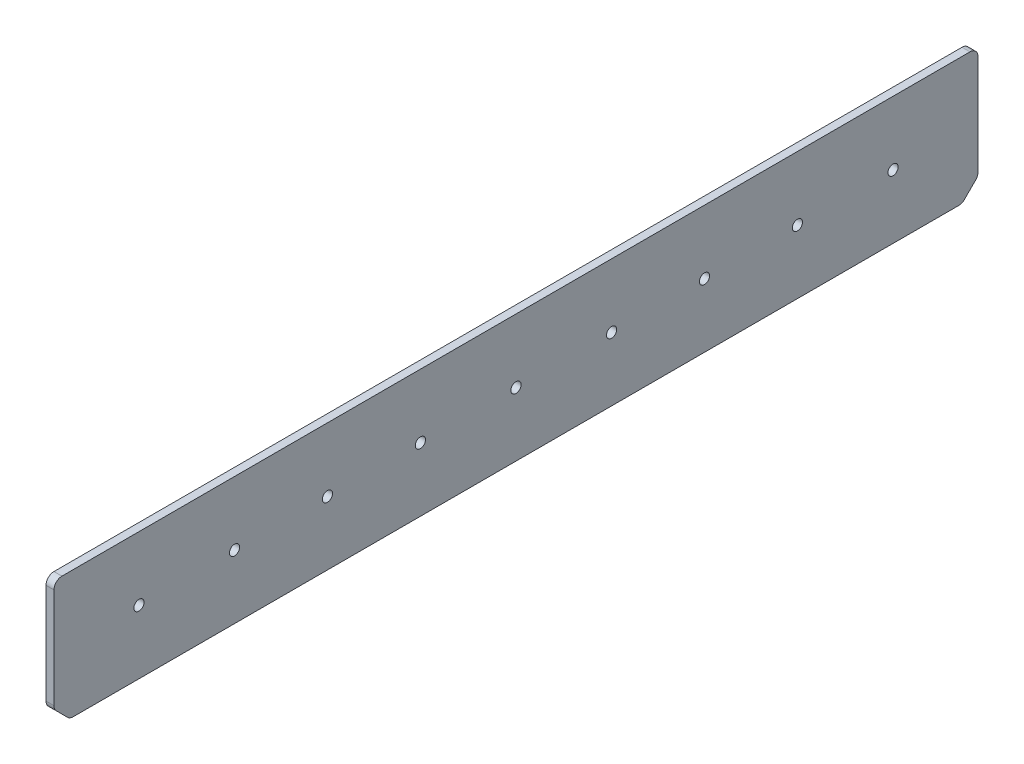
SolidWorks part; units mm, degrees
ref_plane "Front Plane" through (0, 0, 0) normal (0, 0, 1) x (1, 0, 0)
ref_plane "Top Plane" through (0, 0, 0) normal (0, 1, 0) x (1, 0, 0)
ref_plane "Right Plane" through (0, 0, 0) normal (1, 0, 0) x (0, 0, -1)
sketch "Sketch1" plane through (0, 0, 0) normal (1, 0, 0) x (0, 0, -1)
  line L1 (0, 0) -> (368.3, 0)
  line L2 (0, 0) -> (0, 50.8)
  line L3 (0, 50.8) -> (368.3, 50.8)
  line L4 (368.3, 0) -> (368.3, 50.8)
  dimension "D1" = 50.8
  dimension "D2" = 368.3
extrude "Boss-Extrude1" add sketch "Sketch1" along normal blind 3.175
sketch "Sketch2" plane through (3.175, 0, 0) normal (1, 0, 0) x (0, 0, -1)
  circle A0 centre (334.4333, 25.4) radius 2.032 construction
  circle A1 centre (296.3333, 25.4) radius 2.032 construction
  circle A2 centre (259.2917, 25.4) radius 2.032 construction
  circle A3 centre (222.25, 25.4) radius 2.032 construction
  circle A4 centre (184.15, 25.4) radius 2.032 construction
  circle A5 centre (146.05, 25.4) radius 2.032 construction
  circle A6 centre (109.0083, 25.4) radius 2.032 construction
  circle A7 centre (71.9667, 25.4) radius 2.032 construction
  circle A8 centre (33.8667, 25.4) radius 2.032 construction
  circle A9 centre (334.4333, 25.4) radius 2.032
  circle A10 centre (296.3333, 25.4) radius 2.032
  circle A11 centre (259.2917, 25.4) radius 2.032
  circle A12 centre (222.25, 25.4) radius 2.032
  circle A13 centre (184.15, 25.4) radius 2.032
  circle A14 centre (146.05, 25.4) radius 2.032
  circle A15 centre (109.0083, 25.4) radius 2.032
  circle A16 centre (71.9667, 25.4) radius 2.032
  circle A17 centre (33.8667, 25.4) radius 2.032
extrude "Cut-Extrude1" cut sketch "Sketch2" against normal through all
chamfer "Chamfer1" distance 6.35 angle 45 2 edges at (1.5875, 0, 0) (1.5875, 0, -368.3)
fillet "Fillet1" radius 3.175 6 edges at (1.5875, 0, -361.95) (1.5875, 6.35, -368.3) (1.5875, 50.8, -368.3) (1.5875, 0, -6.35) (1.5875, 6.35, 0) (1.5875, 50.8, 0)
